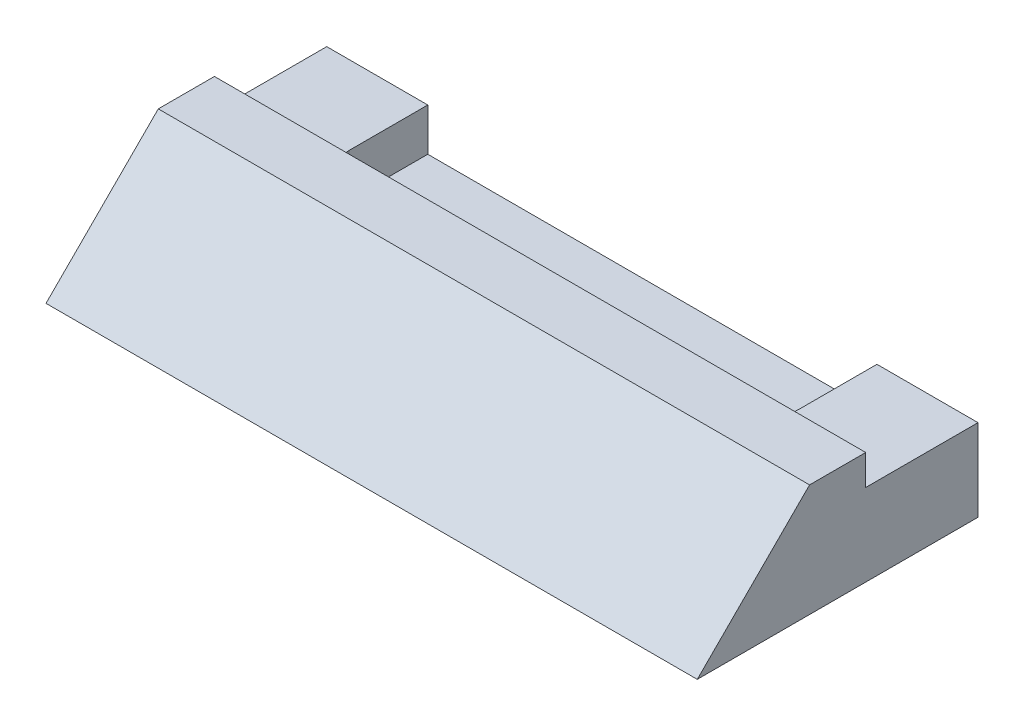
SolidWorks part; units mm, degrees
material "1060 Alloy"
ref_plane "Front Plane" through (0, 0, 0) normal (0, 0, 1) x (1, 0, 0)
ref_plane "Top Plane" through (0, 0, 0) normal (0, 1, 0) x (1, 0, 0)
ref_plane "Right Plane" through (0, 0, 0) normal (1, 0, 0) x (0, 0, -1)
sketch "Sketch1" plane through (0, 0, 0) normal (1, 0, 0) x (0, 0, -1)
  line L0 (0, 0) -> (10, 10)
  line L1 (10, 10) -> (25, 10)
  line L2 (25, 10) -> (25, 0)
  line L3 (25, 0) -> (0, 0)
  dimension "D1" = 45
  dimension "D2" = 10
  dimension "D3" = 15
extrude "Boss-Extrude1" add sketch "Sketch1" along normal blind 58
sketch "Sketch3" plane through (0, 10, 0) normal (0, 1, 0) x (1, 0, 0)
  line L0 (58, 25) -> (0, 25) construction
  line L1 (9, 25) -> (49, 25)
  line L2 (9, 25) -> (9, 15)
  line L3 (9, 15) -> (49, 15)
  line L4 (49, 25) -> (49, 15)
  line L7 (29, 0) -> (29, 15) construction
  line L8 (58, 0) -> (0, 0) construction
  dimension "D2" = 40
  dimension "D3" = 10
extrude "Cut-Extrude2" cut sketch "Sketch3" against normal blind 6.5
sketch "Sketch4" plane through (0, 3.5, 0) normal (0, 1, 0) x (1, 0, 0)
  line L0 (9, 15) -> (49, 15) construction
  line L1 (9, 25) -> (9, 15) construction
  line L3 (49, 15) -> (49, 25) construction
  line L4 (29, 25) -> (29, 20) construction
  line L5 (49, 25) -> (9, 25) construction
  circle A0 centre (14, 20) radius 1.5
  circle A1 centre (29, 20) radius 1.5
  circle A2 centre (44, 20) radius 1.5
  dimension "D1" = 3
  dimension "D2" = 5
  dimension "D3" = 5
  dimension "D5" = 5
extrude "Cut-Extrude3" cut sketch "Sketch4" against normal up to next
sketch "Sketch5" plane through (0, 10, 0) normal (0, 1, 0) x (1, 0, 0)
  line L0 (58, 25) -> (58, 10) construction
  line L1 (0, 25) -> (58, 25)
  line L2 (0, 25) -> (0, 15)
  line L3 (0, 15) -> (58, 15)
  line L4 (58, 25) -> (58, 15)
  line L5 (9, 15) -> (49, 15) construction
extrude "Cut-Extrude4" cut sketch "Sketch5" against normal offset from surface (2.7 mm away) 3.8 up to face at (44, 3.5, -18.5)
fillet "Fillet1" radius 3 2 edges at (49, 5.4, -15) (9, 5.4, -15)
